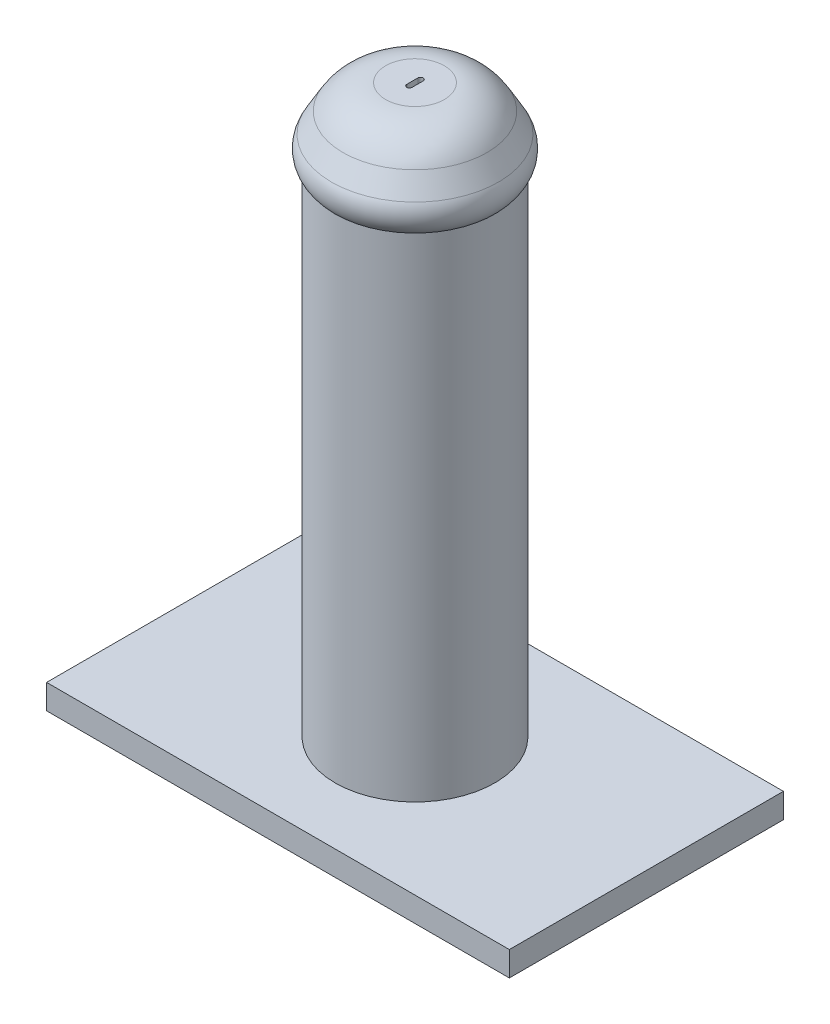
SolidWorks part; units mm, degrees
ref_plane "Front Plane" through (0, 0, 0) normal (0, 0, 1) x (1, 0, 0)
ref_plane "Top Plane" through (0, 0, 0) normal (0, 1, 0) x (1, 0, 0)
ref_plane "Right Plane" through (0, 0, 0) normal (1, 0, 0) x (0, 0, -1)
sketch "Sketch2" plane through (0, 0, 0) normal (0, 1, 0) x (1, 0, 0)
  circle A0 centre (0, 0) radius 32.4113
extrude "Boss-Extrude1" add sketch "Sketch2" along normal blind 200
sketch "Sketch3" plane through (0, 200, 0) normal (0, 1, 0) x (1, 0, 0)
  circle A0 centre (0, 0) radius 40.7644
extrude "Boss-Extrude2" add sketch "Sketch3" along normal blind 30 draft 30
fillet "Fillet1" radius 10 1 edges at (0, 200, 40.7644)
fillet "Fillet2" radius 20 1 edges at (0, 230, 23.4439)
sketch "Sketch4" plane through (0, 230, 0) normal (0, 1, 0) x (1, 0, 0)
  line L0 (0, 2.2583) -> (0, -2.2583) construction
  line L1 (1.0707, 2.2583) -> (1.0707, -2.2583)
  line L2 (-1.0707, 2.2583) -> (-1.0707, -2.2583)
  arc A0 (1.0707, 2.2583) -> (-1.0707, 2.2583) centre (0, 2.2583) ccw
  arc A1 (-1.0707, -2.2583) -> (1.0707, -2.2583) centre (0, -2.2583) ccw
  point P2 (0, 0)
extrude "Cut-Extrude1" cut sketch "Sketch4" against normal blind 10
sketch "Sketch5" plane through (0, 0, 0) normal (0, -1, 0) x (1, 0, 0)
  line L1 (-93.9263, 55.6276) -> (93.9263, 55.6276)
  line L2 (-93.9263, 55.6276) -> (-93.9263, -55.6276)
  line L3 (-93.9263, -55.6276) -> (93.9263, -55.6276)
  line L4 (93.9263, 55.6276) -> (93.9263, -55.6276)
  line L5 (-93.9263, 55.6276) -> (93.9263, -55.6276) construction
  line L6 (-93.9263, -55.6276) -> (93.9263, 55.6276) construction
  point P0 (0, 0)
extrude "Boss-Extrude3" add sketch "Sketch5" along normal blind 10
